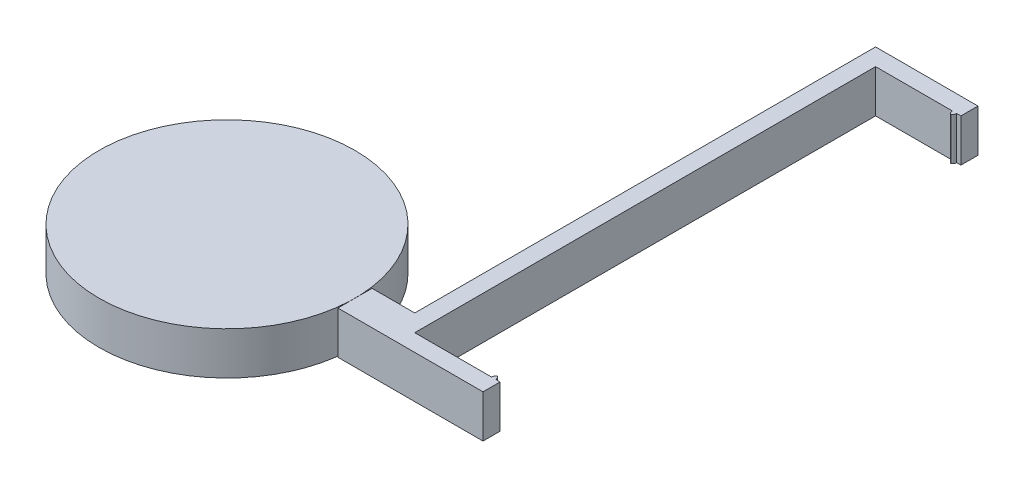
SolidWorks part; units mm, degrees
ref_plane "Front Plane" through (0, 0, 0) normal (0, 0, 1) x (1, 0, 0)
ref_plane "Top Plane" through (0, 0, 0) normal (0, 1, 0) x (1, 0, 0)
ref_plane "Right Plane" through (0, 0, 0) normal (1, 0, 0) x (0, 0, -1)
sketch "Sketch6" plane through (0, 0, 0) normal (1, 0, 0) x (0, 0, -1)
  line L1 (-29, 2.5) -> (29, 2.5)
  line L2 (-29, 2.5) -> (-29, -2.5)
  line L3 (-29, -2.5) -> (29, -2.5)
  line L4 (29, 2.5) -> (29, -2.5)
  line L5 (-29, 2.5) -> (29, -2.5) construction
  line L6 (-29, -2.5) -> (29, 2.5) construction
  point P0 (0, 0)
  dimension "D1" = 58
  dimension "D2" = 5
extrude "Boss-Extrude2" add sketch "Sketch6" along normal blind 12
sketch "Sketch7" plane through (12, 0, 0) normal (1, 0, 0) x (0, 0, -1)
  line L0 (-29, -2.5) -> (29, -2.5) construction
  line L1 (-27, 2.5) -> (27, 2.5)
  line L2 (-27, 2.5) -> (-27, -2.5)
  line L3 (-27, -2.5) -> (27, -2.5)
  line L4 (27, 2.5) -> (27, -2.5)
  line L5 (-27, 2.5) -> (27, -2.5) construction
  line L6 (-27, -2.5) -> (27, 2.5) construction
  line L7 (27, 0) -> (29, 0) construction
  line L8 (29, -2.5) -> (29, 2.5) construction
  point P0 (0, 0)
  dimension "D1" = 2
extrude "Cut-Extrude3" cut sketch "Sketch7" against normal blind 10
sketch "Sketch8" plane through (0, 0, -27) normal (0, 0, 1) x (1, 0, 0)
  line L0 (2, -2.5) -> (12, -2.5) construction
  line L4 (12, 0) -> (11.25, 0) construction
  line L5 (12, -2.5) -> (12, 2.5) construction
  line L6 (11, 2.5) -> (11.5, 2.5)
  line L7 (11, 2.5) -> (11, -2.5)
  line L8 (11, -2.5) -> (11.5, -2.5)
  line L9 (11.5, 2.5) -> (11.5, -2.5)
  line L10 (11, 2.5) -> (11.5, -2.5) construction
  line L11 (11, -2.5) -> (11.5, 2.5) construction
  dimension "D1" = 0.75
  dimension "D2" = 0.5
extrude "Boss-Extrude3" add sketch "Sketch8" along normal blind 0.5
fillet "Fillet1" radius 0.5 2 edges at (11, 0, -26.5) (11.5, 0, -26.5)
ref_plane "Plane1" through (0, 0, 0) normal (0, 0, -1) x (-1, 0, 0)
mirror "Mirror3" about plane through (0, 0, 0) normal (0, 0, -1) of "Fillet1", "Boss-Extrude3"
sketch "Sketch9" plane through (0, 0, 0) normal (-1, 0, 0) x (0, 0, 1)
  line L0 (29, 0) -> (27, 0) construction
  line L1 (29, 2.5) -> (29, -2.5) construction
  line L2 (29, -2.5) -> (-29, -2.5) construction
  line L3 (29, 2.5) -> (25, 2.5)
  line L4 (29, 2.5) -> (29, -2.5)
  line L5 (29, -2.5) -> (25, -2.5)
  line L6 (25, 2.5) -> (25, -2.5)
  line L7 (29, 2.5) -> (25, -2.5) construction
  line L8 (29, -2.5) -> (25, 2.5) construction
  dimension "D1" = 2
  dimension "D2" = 4
extrude "Boss-Extrude4" add sketch "Sketch9" along normal blind 5
sketch "Sketch11" plane through (0, 0, 0) normal (0, 1, 0) x (1, 0, 0)
  line L0 (-5, -27) -> (-20, -27) construction
  line L1 (-5, -29) -> (-5, -25) construction
  circle A0 centre (-20, -27) radius 15
  dimension "D2" = 30
  dimension "D1" = 15
extrude "Boss-Extrude5" add sketch "Sketch11" against normal through all and the other way blind 2.5 separate body
